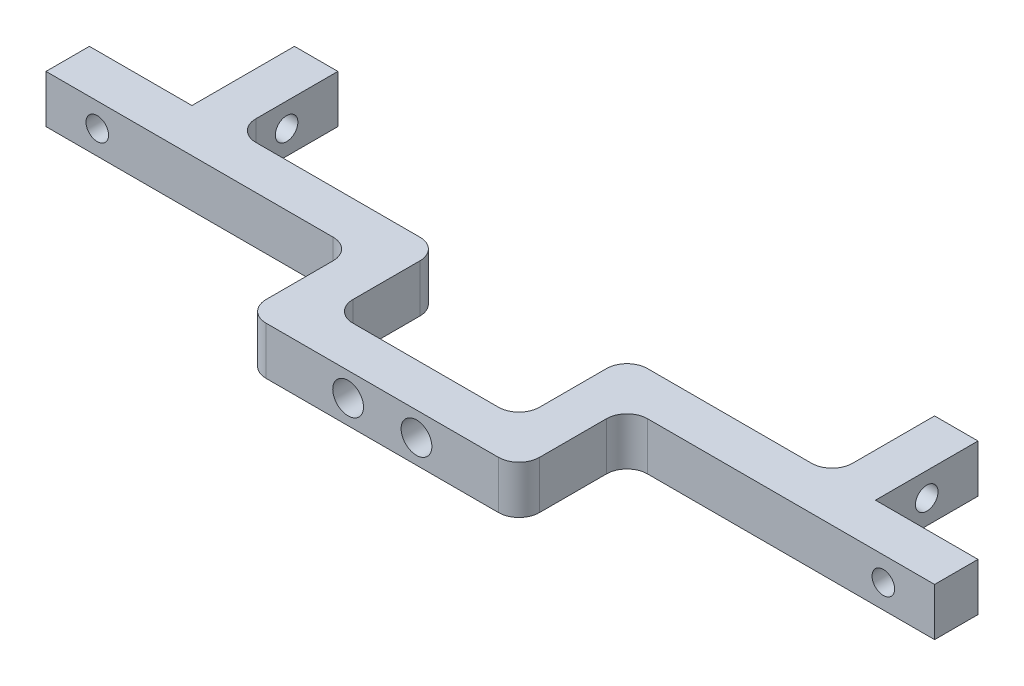
SolidWorks part; units mm, degrees
ref_plane "Front Plane" through (0, 0, 0) normal (0, 0, 1) x (1, 0, 0)
ref_plane "Top Plane" through (0, 0, 0) normal (0, 1, 0) x (1, 0, 0)
ref_plane "Right Plane" through (0, 0, 0) normal (1, 0, 0) x (0, 0, -1)
sketch "Sketch1" plane through (0, 0, 0) normal (0, 1, 0) x (1, 0, 0)
  line L1 (43.65, 15.8) -> (43.65, 30.8)
  line L2 (43.65, 30.8) -> (50, 30.8)
  line L3 (50, 30.8) -> (50, 15.8)
  line L6 (-50, 30.8) -> (-43.65, 30.8)
  line L7 (-43.65, 30.8) -> (-43.65, 15.8)
  line L9 (0, 52.9472) -> (0, -21.9318) construction
  line L10 (50, 15.8) -> (65, 15.8)
  line L13 (65, 15.8) -> (65, 9.45)
  line L15 (-65, 15.8) -> (-65, 9.45)
  line L17 (-50, 15.8) -> (-65, 15.8)
  line L18 (-50, 30.8) -> (-50, 15.8)
  line L20 (-43.65, 15.8) -> (-13.65, 15.8)
  line L22 (-13.65, 15.8) -> (-13.65, 0)
  line L23 (-13.65, 0) -> (13.65, 0)
  line L24 (13.65, 0) -> (13.65, 15.8)
  line L25 (13.65, 15.8) -> (43.65, 15.8)
  line L26 (65, 9.45) -> (20, 9.45)
  line L27 (20, 9.45) -> (20, -6.35)
  line L28 (20, -6.35) -> (-20, -6.35)
  line L29 (-20, -6.35) -> (-20, 9.45)
  line L30 (-20, 9.45) -> (-65, 9.45)
  dimension "D4" = 6.35
  dimension "D5" = 15
  dimension "D6" = 6.35
  dimension "D1" = 30
  dimension "D8" = 30
  dimension "D9" = 27.3
  dimension "D3" = 15
  dimension "D7" = 6.35
  dimension "D10" = 6.35
  dimension "D2" = 15
extrude "Boss-Extrude1" add sketch "Sketch1" along normal blind 7
sketch "Sketch2" plane through (50, 0, 0) normal (1, 0, 0) x (0, 0, -1)
  line L0 (30.8, 7) -> (30.8, 0) construction
  circle A0 centre (23.3, 3.5) radius 1.65
  dimension "D1" = 3.3
  dimension "D2" = 7.5
extrude "Cut-Extrude1" cut sketch "Sketch2" against normal through all
sketch "Sketch3" plane through (0, 0, -15.8) normal (0, 0, -1) x (-1, 0, 0)
  line L0 (-65, 3.5) -> (65, 3.5) construction
  line L3 (-65, 7) -> (-65, 0) construction
  line L4 (65, 7) -> (65, 0) construction
  circle A0 centre (-57.5, 3.5) radius 1.65
  circle A1 centre (57.5, 3.5) radius 1.65
  point P2 (0, 0)
  point P3 (0, 0)
  dimension "D2" = 3.3
  dimension "D4" = 3.3
  dimension "D1" = 7.5
  dimension "D3" = 7.5
fillet "Fillet1" radius 3 10 edges at (-43.65, 3.5, -15.8) (43.65, 3.5, -15.8) (20, 3.5, 6.35) (20, 3.5, -9.45) (-20, 3.5, -9.45) (-20, 3.5, 6.35) (13.65, 3.5, 0) (13.65, 3.5, -15.8) (-13.65, 3.5, -15.8) (-13.65, 3.5, 0)
extrude "Cut-Extrude4" cut sketch "Sketch3" against normal up to surface (6.35 mm away) up to face at (44, 3.5, -9.45)
sketch "Sketch5" plane through (0, 0, 6.35) normal (0, 0, 1) x (1, 0, 0)
  line L0 (-65, 3.5) -> (65, 3.5) construction
  line L1 (-65, 7) -> (-65, 0) construction
  line L2 (65, 7) -> (65, 0) construction
  line L3 (0, 7) -> (0, 0) construction
  line L4 (-17, 7) -> (17, 7) construction
  circle A0 centre (5, 3.5) radius 2.25
  circle A1 centre (-5, 3.5) radius 2.25
  point P13 (0, 0)
  dimension "D1" = 4.5
  dimension "D2" = 5
extrude "Cut-Extrude5" cut sketch "Sketch5" against normal up to surface (6.35 mm away) up to face at (0, 3.5, 0)
equation "\"D6@Sketch1\"=\"D4@Sketch1\""
